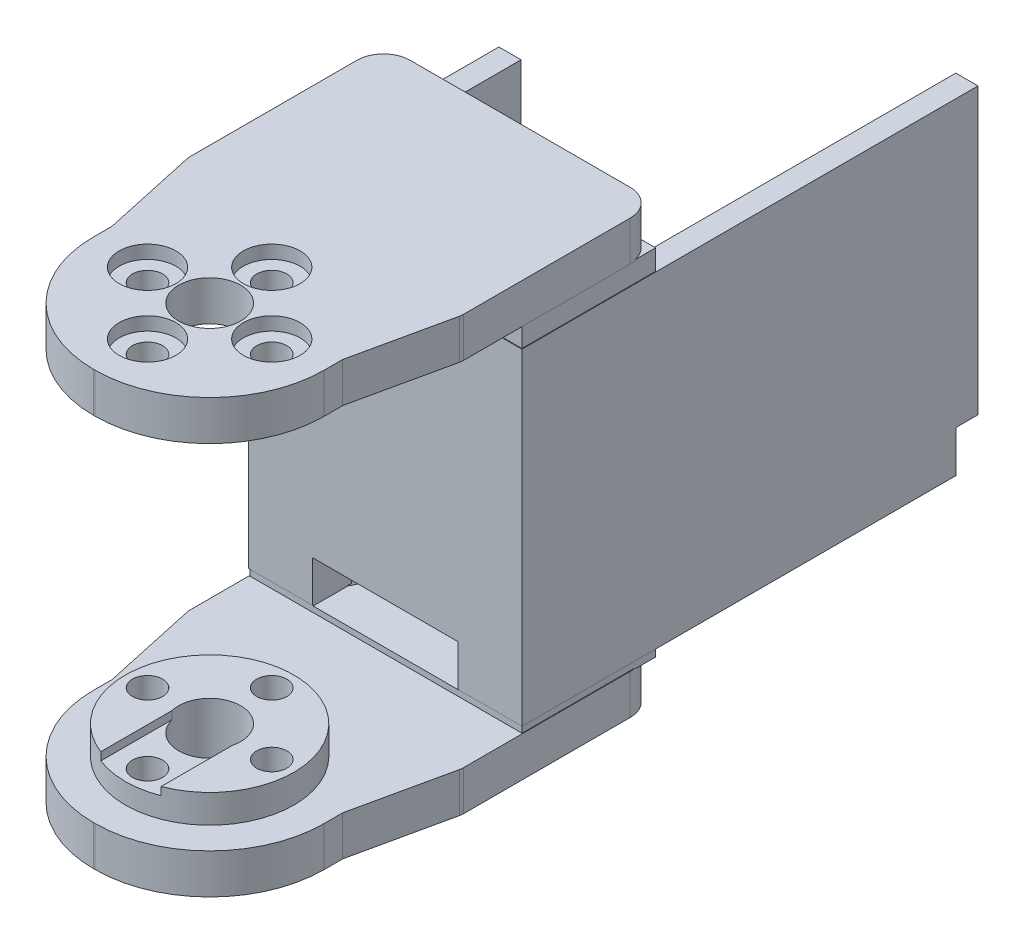
SolidWorks part; units mm, degrees
ref_plane "Front Plane" through (0, 0, 0) normal (0, 0, 1) x (1, 0, 0)
ref_plane "Top Plane" through (0, 0, 0) normal (0, 1, 0) x (1, 0, 0)
ref_plane "Right Plane" through (0, 0, 0) normal (1, 0, 0) x (0, 0, -1)
ref_plane "PY_p18_800" through (0, 18.8, 0) normal (0, 1, 0) x (1, 0, 0)
sketch "S_prism1" plane through (0, 18.8, 0) normal (0, 1, 0) x (1, 0, 0)
  line L0 (-13, 2) -> (-15.354, 12.7893)
  line L1 (-15.4, 13.2156) -> (-15.4, 32)
  line L2 (-12.4, 35) -> (12.4, 35)
  line L3 (15.4, 32) -> (15.4, 13.2156)
  line L4 (15.354, 12.7893) -> (13, 2)
  line L5 (13, 2) -> (13, -0.1)
  line L6 (0.1, -13) -> (-0.1, -13)
  line L7 (-13, -0.1) -> (-13, 2)
  arc A0 (-15.354, 12.7893) -> (-15.4, 13.2156) centre (-13.4076, 13.215) cw
  arc A1 (-15.4, 32) -> (-12.4, 35) centre (-12.3999, 31.9999) cw
  arc A2 (12.4, 35) -> (15.4, 32) centre (12.3999, 31.9999) cw
  arc A3 (15.4, 13.2156) -> (15.354, 12.7893) centre (13.4076, 13.215) cw
  arc A4 (13, -0.1) -> (0.1, -13) centre (0.1001, -0.1001) cw
  arc A5 (-0.1, -13) -> (-13, -0.1) centre (-0.1001, -0.1001) cw
extrude "Boss_1" add sketch "S_prism1" along normal blind 4.5
ref_plane "PY_m20_950" through (0, -20.95, 0) normal (0, 1, 0) x (1, 0, 0)
sketch "S_cyl2" plane through (0, -20.95, 0) normal (0, 1, 0) x (1, 0, 0)
  circle A0 centre (0, 0) radius 9.5
  dimension "D1_S_cyl2" = 19
extrude "Boss_2" add sketch "S_cyl2" along normal blind 3.2
ref_plane "PY_m25_450" through (0, -25.45, 0) normal (0, 1, 0) x (1, 0, 0)
sketch "S_prism3" plane through (0, -25.45, 0) normal (0, 1, 0) x (1, 0, 0)
  line L0 (-13, 2) -> (-15.354, 12.7893)
  line L1 (-15.4, 13.2156) -> (-15.4, 32)
  line L2 (-12.4, 35) -> (12.4, 35)
  line L3 (15.4, 32) -> (15.4, 13.2156)
  line L4 (15.354, 12.7893) -> (13, 2)
  line L5 (13, 2) -> (13, -0.1)
  line L6 (0.1, -13) -> (-0.1, -13)
  line L7 (-13, -0.1) -> (-13, 2)
  arc A0 (-15.354, 12.7893) -> (-15.4, 13.2156) centre (-13.4076, 13.215) cw
  arc A1 (-15.4, 32) -> (-12.4, 35) centre (-12.3999, 31.9999) cw
  arc A2 (12.4, 35) -> (15.4, 32) centre (12.3999, 31.9999) cw
  arc A3 (15.4, 13.2156) -> (15.354, 12.7893) centre (13.4076, 13.215) cw
  arc A4 (13, -0.1) -> (0.1, -13) centre (0.1001, -0.1001) cw
  arc A5 (-0.1, -13) -> (-13, -0.1) centre (-0.1001, -0.1001) cw
extrude "Boss_3" add sketch "S_prism3" along normal blind 4.5
ref_plane "PZ_m22_300" through (0, 0, -22.3) normal (0, 0, 1) x (1, 0, 0)
sketch "S_box4" plane through (0, 0, -22.3) normal (0, 0, 1) x (1, 0, 0)
  line L0 (-15.4, -20.2) -> (15.4, -20.2)
  line L1 (15.4, -20.2) -> (15.4, 16.6)
  line L2 (15.4, 16.6) -> (-15.4, 16.6)
  line L3 (-15.4, 16.6) -> (-15.4, -20.2)
  dimension "P1" = 15.4
  dimension "P2" = 20.2
  dimension "P3" = 15.4
  dimension "P4" = 20.2
  dimension "P5" = 15.4
  dimension "P6" = 16.6
  dimension "P7" = 15.4
  dimension "P8" = 16.6
extrude "Boss_4" add sketch "S_box4" along normal blind 2.5
ref_plane "PZ_m71_200" through (0, 0, -71.2) normal (0, 0, 1) x (1, 0, 0)
sketch "S_box5" plane through (0, 0, -71.2) normal (0, 0, 1) x (1, 0, 0)
  line L0 (12.9, -20.2) -> (15.4, -20.2)
  line L1 (15.4, -20.2) -> (15.4, 16.6)
  line L2 (15.4, 16.6) -> (12.9, 16.6)
  line L3 (12.9, 16.6) -> (12.9, -20.2)
  dimension "P1" = 12.9
  dimension "P2" = 20.2
  dimension "P3" = 15.4
  dimension "P4" = 20.2
  dimension "P5" = 15.4
  dimension "P6" = 16.6
  dimension "P7" = 12.9
  dimension "P8" = 16.6
extrude "Boss_5" add sketch "S_box5" along normal blind 51.4
sketch "S_box6" plane through (0, 0, -71.2) normal (0, 0, 1) x (1, 0, 0)
  line L0 (-15.4, -20.2) -> (15.4, -20.2)
  line L1 (15.4, -20.2) -> (15.4, -15.6)
  line L2 (15.4, -15.6) -> (-15.4, -15.6)
  line L3 (-15.4, -15.6) -> (-15.4, -20.2)
  dimension "P1" = 15.4
  dimension "P2" = 20.2
  dimension "P3" = 15.4
  dimension "P4" = 20.2
  dimension "P5" = 15.4
  dimension "P6" = 15.6
  dimension "P7" = 15.4
  dimension "P8" = 15.6
extrude "Boss_6" add sketch "S_box6" along normal blind 51.4
ref_plane "PZ_m48_000" through (0, 0, -48) normal (0, 0, 1) x (1, 0, 0)
sketch "S_box7" plane through (0, 0, -48) normal (0, 0, 1) x (1, 0, 0)
  line L0 (-15.4, -20.2) -> (-12.9, -20.2)
  line L1 (-12.9, -20.2) -> (-12.9, 16.6)
  line L2 (-12.9, 16.6) -> (-15.4, 16.6)
  line L3 (-15.4, 16.6) -> (-15.4, -20.2)
  dimension "P1" = 15.4
  dimension "P2" = 20.2
  dimension "P3" = 12.9
  dimension "P4" = 20.2
  dimension "P5" = 12.9
  dimension "P6" = 16.6
  dimension "P7" = 15.4
  dimension "P8" = 16.6
extrude "Boss_7" add sketch "S_box7" along normal blind 28.2
ref_plane "PZ_m34_930" through (0, 0, -34.93) normal (0, 0, 1) x (1, 0, 0)
sketch "S_box8" plane through (0, 0, -34.93) normal (0, 0, 1) x (1, 0, 0)
  line L0 (-15.33, 16.5) -> (15.33, 16.5)
  line L1 (15.33, 16.5) -> (15.33, 18.9)
  line L2 (15.33, 18.9) -> (-15.33, 18.9)
  line L3 (-15.33, 18.9) -> (-15.33, 16.5)
  dimension "P1" = 15.33
  dimension "P2" = 16.5
  dimension "P3" = 15.33
  dimension "P4" = 16.5
  dimension "P5" = 15.33
  dimension "P6" = 18.9
  dimension "P7" = 15.33
  dimension "P8" = 18.9
extrude "Boss_8" add sketch "S_box8" along normal blind 15.06
sketch "S_box9" plane through (0, 0, -34.93) normal (0, 0, 1) x (1, 0, 0)
  line L0 (-15.33, -21.05) -> (15.33, -21.05)
  line L1 (15.33, -21.05) -> (15.33, -20.1)
  line L2 (15.33, -20.1) -> (-15.33, -20.1)
  line L3 (-15.33, -20.1) -> (-15.33, -21.05)
  dimension "P1" = 15.33
  dimension "P2" = 21.05
  dimension "P3" = 15.33
  dimension "P4" = 21.05
  dimension "P5" = 15.33
  dimension "P6" = 20.1
  dimension "P7" = 15.33
  dimension "P8" = 20.1
extrude "Boss_9" add sketch "S_box9" along normal blind 15.06
ref_plane "PY_p18_700" through (0, 18.7, 0) normal (0, 1, 0) x (1, 0, 0)
sketch "S_hole10" plane through (0, 18.7, 0) normal (0, 1, 0) x (1, 0, 0)
  circle A0 centre (0, 0) radius 3.5
  dimension "D1_S_hole10" = 7
extrude "Hole_10" cut sketch "S_hole10" along normal blind 4.7
sketch "S_hole11" plane through (0, 18.7, 0) normal (0, 1, 0) x (1, 0, 0)
  circle A0 centre (7, 0) radius 1.7
  dimension "D1_S_hole11" = 3.4
  dimension "P2" = 7
extrude "Hole_11" cut sketch "S_hole11" along normal blind 4.7
sketch "S_hole12" plane through (0, 18.7, 0) normal (0, 1, 0) x (1, 0, 0)
  circle A0 centre (0, -7) radius 1.7
  dimension "D1_S_hole12" = 3.4
  dimension "P2" = 7
extrude "Hole_12" cut sketch "S_hole12" along normal blind 4.7
sketch "S_hole13" plane through (0, 18.7, 0) normal (0, 1, 0) x (1, 0, 0)
  circle A0 centre (-7, 0) radius 1.7
  dimension "D1_S_hole13" = 3.4
  dimension "P2" = 7
extrude "Hole_13" cut sketch "S_hole13" along normal blind 4.7
sketch "S_hole14" plane through (0, 18.7, 0) normal (0, 1, 0) x (1, 0, 0)
  circle A0 centre (0, 7) radius 1.7
  dimension "D1_S_hole14" = 3.4
  dimension "P2" = 7
extrude "Hole_14" cut sketch "S_hole14" along normal blind 4.7
ref_plane "PY_p21_800" through (0, 21.8, 0) normal (0, 1, 0) x (1, 0, 0)
sketch "S_hole15" plane through (0, 21.8, 0) normal (0, 1, 0) x (1, 0, 0)
  circle A0 centre (7, 0) radius 3.2
  dimension "D1_S_hole15" = 6.4
  dimension "P2" = 7
extrude "Hole_15" cut sketch "S_hole15" along normal blind 1.6
sketch "S_hole16" plane through (0, 21.8, 0) normal (0, 1, 0) x (1, 0, 0)
  circle A0 centre (0, -7) radius 3.2
  dimension "D1_S_hole16" = 6.4
  dimension "P2" = 7
extrude "Hole_16" cut sketch "S_hole16" along normal blind 1.6
sketch "S_hole17" plane through (0, 21.8, 0) normal (0, 1, 0) x (1, 0, 0)
  circle A0 centre (-7, 0) radius 3.2
  dimension "D1_S_hole17" = 6.4
  dimension "P2" = 7
extrude "Hole_17" cut sketch "S_hole17" along normal blind 1.6
sketch "S_hole18" plane through (0, 21.8, 0) normal (0, 1, 0) x (1, 0, 0)
  circle A0 centre (0, 7) radius 3.2
  dimension "D1_S_hole18" = 6.4
  dimension "P2" = 7
extrude "Hole_18" cut sketch "S_hole18" along normal blind 1.6
ref_plane "PY_m25_550" through (0, -25.55, 0) normal (0, 1, 0) x (1, 0, 0)
sketch "S_hole19" plane through (0, -25.55, 0) normal (0, 1, 0) x (1, 0, 0)
  circle A0 centre (0, 0) radius 3.5
  dimension "D1_S_hole19" = 7
extrude "Hole_19" cut sketch "S_hole19" along normal blind 7.9
sketch "S_hole20" plane through (0, -25.55, 0) normal (0, 1, 0) x (1, 0, 0)
  circle A0 centre (7, 0) radius 1.7
  dimension "D1_S_hole20" = 3.4
  dimension "P2" = 7
extrude "Hole_20" cut sketch "S_hole20" along normal blind 7.9
sketch "S_hole21" plane through (0, -25.55, 0) normal (0, 1, 0) x (1, 0, 0)
  circle A0 centre (0, -7) radius 1.7
  dimension "D1_S_hole21" = 3.4
  dimension "P2" = 7
extrude "Hole_21" cut sketch "S_hole21" along normal blind 7.9
sketch "S_hole22" plane through (0, -25.55, 0) normal (0, 1, 0) x (1, 0, 0)
  circle A0 centre (-7, 0) radius 1.7
  dimension "D1_S_hole22" = 3.4
  dimension "P2" = 7
extrude "Hole_22" cut sketch "S_hole22" along normal blind 7.9
sketch "S_hole23" plane through (0, -25.55, 0) normal (0, 1, 0) x (1, 0, 0)
  circle A0 centre (0, 7) radius 1.7
  dimension "D1_S_hole23" = 3.4
  dimension "P2" = 7
extrude "Hole_23" cut sketch "S_hole23" along normal blind 7.9
sketch "S_hole24" plane through (0, -25.55, 0) normal (0, 1, 0) x (1, 0, 0)
  circle A0 centre (7, 0) radius 3.2
  dimension "D1_S_hole24" = 6.4
  dimension "P2" = 7
extrude "Hole_24" cut sketch "S_hole24" along normal blind 2.1
sketch "S_hole25" plane through (0, -25.55, 0) normal (0, 1, 0) x (1, 0, 0)
  circle A0 centre (0, -7) radius 3.2
  dimension "D1_S_hole25" = 6.4
  dimension "P2" = 7
extrude "Hole_25" cut sketch "S_hole25" along normal blind 2.1
sketch "S_hole26" plane through (0, -25.55, 0) normal (0, 1, 0) x (1, 0, 0)
  circle A0 centre (-7, 0) radius 3.2
  dimension "D1_S_hole26" = 6.4
  dimension "P2" = 7
extrude "Hole_26" cut sketch "S_hole26" along normal blind 2.1
sketch "S_hole27" plane through (0, -25.55, 0) normal (0, 1, 0) x (1, 0, 0)
  circle A0 centre (0, 7) radius 3.2
  dimension "D1_S_hole27" = 6.4
  dimension "P2" = 7
extrude "Hole_27" cut sketch "S_hole27" along normal blind 2.1
sketch "S_cut28" plane through (0, 0, 0) normal (0, 0, 1) x (1, 0, 0)
  line L0 (-3.4, -18.65) -> (3.4, -18.65)
  line L1 (3.4, -18.65) -> (3.4, -17.65)
  line L2 (3.4, -17.65) -> (-3.4, -17.65)
  line L3 (-3.4, -17.65) -> (-3.4, -18.65)
  dimension "P1" = 3.4
  dimension "P2" = 18.65
  dimension "P3" = 3.4
  dimension "P4" = 18.65
  dimension "P5" = 3.4
  dimension "P6" = 17.65
  dimension "P7" = 3.4
  dimension "P8" = 17.65
extrude "Pocket_28" cut sketch "S_cut28" along normal blind 10
ref_plane "PY_m20_300" through (0, -20.3, 0) normal (0, 1, 0) x (1, 0, 0)
sketch "S_hole29" plane through (0, -20.3, 0) normal (0, 1, 0) x (1, 0, 0)
  circle A0 centre (0, 58) radius 10.5
  dimension "D1_S_hole29" = 21
  dimension "P2" = 58
extrude "Hole_29" cut sketch "S_hole29" along normal blind 4.8
ref_plane "PZ_m47_100" through (0, 0, -47.1) normal (0, 0, 1) x (1, 0, 0)
sketch "S_cut30" plane through (0, 0, -47.1) normal (0, 0, 1) x (1, 0, 0)
  line L0 (-9.7, -20.3) -> (9.7, -20.3)
  line L1 (9.7, -20.3) -> (9.7, -15.55)
  line L2 (9.7, -15.55) -> (-9.7, -15.55)
  line L3 (-9.7, -15.55) -> (-9.7, -20.3)
  dimension "P1" = 9.7
  dimension "P2" = 20.3
  dimension "P3" = 9.7
  dimension "P4" = 20.3
  dimension "P5" = 9.7
  dimension "P6" = 15.55
  dimension "P7" = 9.7
  dimension "P8" = 15.55
extrude "Pocket_30" cut sketch "S_cut30" along normal blind 19.5
ref_plane "PZ_m27_600" through (0, 0, -27.6) normal (0, 0, 1) x (1, 0, 0)
sketch "S_cut31" plane through (0, 0, -27.6) normal (0, 0, 1) x (1, 0, 0)
  line L0 (-8.2, -20.3) -> (8.2, -20.3)
  line L1 (8.2, -20.3) -> (8.2, -15.55)
  line L2 (8.2, -15.55) -> (-8.2, -15.55)
  line L3 (-8.2, -15.55) -> (-8.2, -20.3)
  dimension "P1" = 8.2
  dimension "P2" = 20.3
  dimension "P3" = 8.2
  dimension "P4" = 20.3
  dimension "P5" = 8.2
  dimension "P6" = 15.55
  dimension "P7" = 8.2
  dimension "P8" = 15.55
extrude "Pocket_31" cut sketch "S_cut31" along normal blind 8.3
ref_plane "PZ_m58_000" through (0, 0, -58) normal (0, 0, 1) x (1, 0, 0)
sketch "S_cut32" plane through (0, 0, -58) normal (0, 0, 1) x (1, 0, 0)
  line L0 (-3.5, -20.3) -> (3.5, -20.3)
  line L1 (3.5, -20.3) -> (3.5, -15.55)
  line L2 (3.5, -15.55) -> (-3.5, -15.55)
  line L3 (-3.5, -15.55) -> (-3.5, -20.3)
  dimension "P1" = 3.5
  dimension "P2" = 20.3
  dimension "P3" = 3.5
  dimension "P4" = 20.3
  dimension "P5" = 3.5
  dimension "P6" = 15.55
  dimension "P7" = 3.5
  dimension "P8" = 15.55
extrude "Pocket_32" cut sketch "S_cut32" along normal blind 11
ref_plane "PZ_m71_700" through (0, 0, -71.7) normal (0, 0, 1) x (1, 0, 0)
sketch "S_cut33" plane through (0, 0, -71.7) normal (0, 0, 1) x (1, 0, 0)
  line L0 (-10, -20.4) -> (10, -20.4)
  line L1 (10, -20.4) -> (10, -17.5)
  line L2 (10, -17.5) -> (-10, -17.5)
  line L3 (-10, -17.5) -> (-10, -20.4)
  dimension "P1" = 10
  dimension "P2" = 20.4
  dimension "P3" = 10
  dimension "P4" = 20.4
  dimension "P5" = 10
  dimension "P6" = 17.5
  dimension "P7" = 10
  dimension "P8" = 17.5
extrude "Pocket_33" cut sketch "S_cut33" along normal blind 13.7
sketch "S_hole34" plane through (0, -20.3, 0) normal (0, 1, 0) x (1, 0, 0)
  circle A0 centre (-10.25, 25.25) radius 1.1
  dimension "D1_S_hole34" = 2.2
  dimension "P2" = 10.25
  dimension "P3" = 25.25
extrude "Hole_34" cut sketch "S_hole34" along normal blind 4.8
sketch "S_hole35" plane through (0, -20.3, 0) normal (0, 1, 0) x (1, 0, 0)
  circle A0 centre (-10.25, 25.25) radius 2.3
  dimension "D1_S_hole35" = 4.6
  dimension "P2" = 10.25
  dimension "P3" = 25.25
extrude "Hole_35" cut sketch "S_hole35" along normal blind 1.7
sketch "S_hole36" plane through (0, -20.3, 0) normal (0, 1, 0) x (1, 0, 0)
  circle A0 centre (10.25, 25.25) radius 1.1
  dimension "D1_S_hole36" = 2.2
  dimension "P2" = 10.25
  dimension "P3" = 25.25
extrude "Hole_36" cut sketch "S_hole36" along normal blind 4.8
sketch "S_hole37" plane through (0, -20.3, 0) normal (0, 1, 0) x (1, 0, 0)
  circle A0 centre (10.25, 25.25) radius 2.3
  dimension "D1_S_hole37" = 4.6
  dimension "P2" = 10.25
  dimension "P3" = 25.25
extrude "Hole_37" cut sketch "S_hole37" along normal blind 1.7
ref_plane "PZ_m71_300" through (0, 0, -71.3) normal (0, 0, 1) x (1, 0, 0)
sketch "S_cut38" plane through (0, 0, -71.3) normal (0, 0, 1) x (1, 0, 0)
  line L0 (-15.5, -20.3) -> (15.5, -20.3)
  line L1 (15.5, -20.3) -> (15.5, -15.5)
  line L2 (15.5, -15.5) -> (-15.5, -15.5)
  line L3 (-15.5, -15.5) -> (-15.5, -20.3)
  dimension "P1" = 15.5
  dimension "P2" = 20.3
  dimension "P3" = 15.5
  dimension "P4" = 20.3
  dimension "P5" = 15.5
  dimension "P6" = 15.5
  dimension "P7" = 15.5
  dimension "P8" = 15.5
extrude "Pocket_38" cut sketch "S_cut38" along normal blind 2.6
ref_plane "PZ_m68_800" through (0, 0, -68.8) normal (0, 0, 1) x (1, 0, 0)
sketch "S_cut39" plane through (0, 0, -68.8) normal (0, 0, 1) x (1, 0, 0)
  line L0 (-9.5, -20.3) -> (9.5, -20.3)
  line L1 (9.5, -20.3) -> (9.5, -15.55)
  line L2 (9.5, -15.55) -> (-9.5, -15.55)
  line L3 (-9.5, -15.55) -> (-9.5, -20.3)
  dimension "P1" = 9.5
  dimension "P2" = 20.3
  dimension "P3" = 9.5
  dimension "P4" = 20.3
  dimension "P5" = 9.5
  dimension "P6" = 15.55
  dimension "P7" = 9.5
  dimension "P8" = 15.55
extrude "Pocket_39" cut sketch "S_cut39" along normal blind 22.2
ref_plane "PZ_m49_900" through (0, 0, -49.9) normal (0, 0, 1) x (1, 0, 0)
sketch "S_cut40" plane through (0, 0, -49.9) normal (0, 0, 1) x (1, 0, 0)
  line L0 (-7.5, 16.2) -> (7.5, 16.2)
  line L1 (7.5, 16.2) -> (7.5, 17.75)
  line L2 (7.5, 17.75) -> (-7.5, 17.75)
  line L3 (-7.5, 17.75) -> (-7.5, 16.2)
  dimension "P1" = 7.5
  dimension "P2" = 16.2
  dimension "P3" = 7.5
  dimension "P4" = 16.2
  dimension "P5" = 7.5
  dimension "P6" = 17.75
  dimension "P7" = 7.5
  dimension "P8" = 17.75
extrude "Pocket_40" cut sketch "S_cut40" along normal blind 27.4
sketch "S_hole41" plane through (0, -25.55, 0) normal (0, 1, 0) x (1, 0, 0)
  circle A0 centre (-10.25, 25.25) radius 2.5
  dimension "D1_S_hole41" = 5
  dimension "P2" = 10.25
  dimension "P3" = 25.25
extrude "Hole_41" cut sketch "S_hole41" along normal blind 5.3
sketch "S_hole42" plane through (0, -25.55, 0) normal (0, 1, 0) x (1, 0, 0)
  circle A0 centre (10.25, 25.25) radius 2.5
  dimension "D1_S_hole42" = 5
  dimension "P2" = 10.25
  dimension "P3" = 25.25
extrude "Hole_42" cut sketch "S_hole42" along normal blind 5.3
equation "\"plate_t\" = 3"
equation "\"clearance\" = 0.5"
